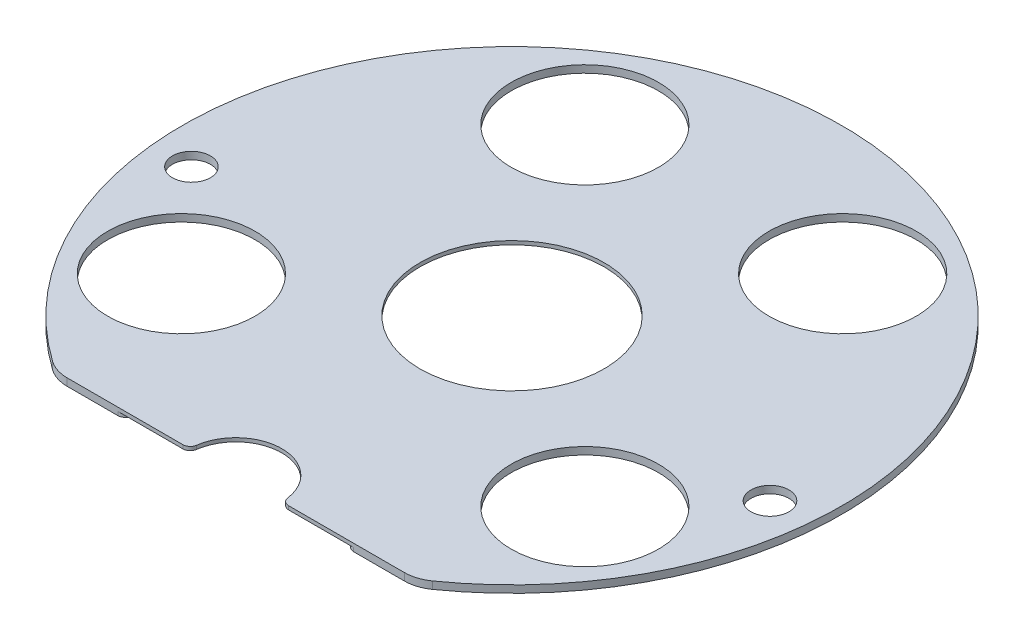
SolidWorks part; units mm, degrees
material "6063-T6"
ref_plane "Front Plane" through (0, 0, 0) normal (0, 0, 1) x (1, 0, 0)
ref_plane "Top Plane" through (0, 0, 0) normal (0, 1, 0) x (1, 0, 0)
ref_plane "Right Plane" through (0, 0, 0) normal (1, 0, 0) x (0, 0, -1)
sketch "Sketch1" plane through (0, 0, 0) normal (0, 1, 0) x (1, 0, 0)
  line L0 (0, 89.5) -> (0, -75) construction
  line L2 (-89.5, 0) -> (89.5, 0) construction
  line L3 (-48.839, -75) -> (48.839, -75)
  arc A0 (48.839, -75) -> (-48.839, -75) centre (0, 0) ccw
  dimension "D1" = 179
  dimension "D2" = 75
extrude "Boss-Extrude1" add sketch "Sketch1" against normal blind 2
sketch "Sketch9" plane through (0, 0, 0) normal (0, 1, 0) x (1, 0, 0)
  line L0 (0, 89.5) -> (0, -75) construction
  line L1 (48.839, -75) -> (-48.839, -75) construction
  line L2 (78.5412, -8.5017) -> (-78.5412, -8.5017) construction
  arc A12 (48.839, -75) -> (-48.839, -75) centre (0, 0) ccw construction
  circle A13 centre (78.5412, -8.5017) radius 5.15
  circle A15 centre (-78.5412, -8.5017) radius 5.15
  point P8 (0, -8.5017)
  dimension "D3" = 10.3
  dimension "D4" = 10.3
  dimension "D2" = 66.4983
  dimension "D1" = 157.0824
extrude "Cut-Extrude3" cut sketch "Sketch9" against normal through all
sketch "Vision Pattern" plane through (0, 0, 0) normal (0, 1, 0) x (1, 0, 0)
  line L0 (64.8074, -55) -> (-64.8074, -55) construction
  line L1 (0, 0) -> (0, -55) construction
  circle A0 centre (0, 0) radius 85 construction
  circle A1 centre (0, 0) radius 25
  circle A2 centre (54.7723, -35) radius 20
  circle A3 centre (-54.7723, -35) radius 20
  circle A4 centre (35, 54.7723) radius 20
  circle A5 centre (-35, 54.7723) radius 20
  circle A6 centre (0, 0) radius 65 construction
  dimension "D1" = 170
  dimension "D3" = 50
  dimension "D4" = 40
  dimension "D2" = 55
  dimension "D5" = 35
  dimension "D8" = 65
  dimension "D6" = 35
  dimension "D7" = 35
extrude "Cut-Extrude4" cut sketch "Vision Pattern" against normal through all
fillet "Fillet1" radius 10 2 edges at (-48.839, -1, 75) (48.839, -1, 75)
ref_plane "Plane2" through (0, 0, -97) normal (0, 0, 1) x (1, 0, 0)
ref_plane "Plane3" through (0, 0, 5) normal (0, 0, 1) x (1, 0, 0)
sketch "Sketch18" plane through (0, 0, 5) normal (0, 0, 1) x (1, 0, 0)
  line L0 (62.8547, -3.6) -> (67.1453, -3.6)
  line L1 (67.1453, -3.6) -> (66.025, -2)
  line L2 (66.025, -2) -> (63.975, -2)
  line L3 (63.975, -2) -> (62.8547, -3.6)
  line L4 (-45.7739, -2) -> (45.7739, -2) construction
  line L6 (-45.7739, -2) -> (45.7739, -2) construction
  point P8 (0, -2)
  point P9 (65, -2)
  dimension "D1" = 55
  dimension "D2" = 55
  dimension "D3" = 1.6
  dimension "D4" = 2.05
  dimension "D5" = 65
extrude "Boss-Extrude4" add sketch "Sketch18" against normal blind 50
mirror "Mirror2" about plane through (0, 0, 0) normal (1, 0, 0) of "Boss-Extrude4"
sketch "Sketch12" plane through (0, -2, 0) normal (0, -1, 0) x (1, 0, 0)
  line L0 (-45.7739, 75) -> (45.7739, 75) construction
  line L1 (-30, 75) -> (30, 75)
  line L2 (-30, 75) -> (-30, -31)
  line L3 (-30, -31) -> (30, -31)
  line L4 (30, 75) -> (30, -31)
  point P6 (0, -31)
  dimension "D1" = 60
  dimension "D2" = 31
extrude "Cut-Extrude5" cut sketch "Sketch12" against normal blind 1
sketch "Sketch16" plane through (0, 0, 0) normal (0, 1, 0) x (1, 0, 0)
  line L0 (-45.7739, -75) -> (45.7739, -75) construction
  circle A0 centre (0, -75) radius 12.5
  dimension "D1" = 25
extrude "Cut-Extrude9" cut sketch "Sketch16" against normal blind 20
sketch "Sketch17" plane through (0, -1, 0) normal (0, -1, 0) x (1, 0, 0)
  line L2 (-30, 75) -> (21.25, 75) construction
  line L3 (30, 75) -> (12.5, 75) construction
  line L4 (-30, 75) -> (-30, -31) construction
  circle A1 centre (-22, -25) radius 0.75
  dimension "D1" = 8
  dimension "D3" = 1.5
  dimension "D4" = 100
extrude "Boss-Extrude3" add sketch "Sketch17" along normal blind 0.425 contours A1
mirror "Mirror1" about plane through (0, 0, 0) normal (1, 0, 0) of "Boss-Extrude3"
chamfer "Chamfer1" distance 1.8 angle 65 6 edges at (63.4148, -2.8, 5) (66.5852, -2.8, 5) (65, -3.6, 5) (-65, -3.6, 5) (-65, -3.6, -45) (65, -3.6, -45)
chamfer "Chamfer2" distance 1 angle 60 8 edges at (-66.5852, -2.8, 2.8555) (-63.4148, -2.8, 2.8555) (63.4148, -2.8, 2.8555) (66.5852, -2.8, 2.8555) (-66.5852, -2.8, -42.8555) (-63.4148, -2.8, -42.8555) (63.4148, -2.8, -42.8555) (66.5852, -2.8, -42.8555)
fillet "Fillet3" radius 0.1 16 edges at (-63.3761, -3.6, 0.1422) (-62.8547, -3.6, -20) (-67.1453, -3.6, -20) (-66.6239, -3.6, 0.1422) (-65, -3.6, 1.1399) (66.6239, -3.6, 0.1422) (67.1453, -3.6, -20) (62.8547, -3.6, -20) (63.3761, -3.6, 0.1422) (65, -3.6, 1.1399) (-65, -3.6, -41.1399) (65, -3.6, -41.1399) (-63.3761, -3.6, -40.1422) (-66.6239, -3.6, -40.1422) (66.6239, -3.6, -40.1422) (63.3761, -3.6, -40.1422)
fillet "Fillet2" radius 0.4 2 edges at (22, -1.425, -25.75) (-22, -1.425, -25.75)
sketch "Sketch19" plane through (0, -3.6, 0) normal (0, -1, 0) x (1, 0, 0)
  line L1 (95.4806, 15.8936) -> (57.8669, 15.8936)
  line L2 (95.4806, 15.8936) -> (95.4806, -73.6368)
  line L3 (95.4806, -73.6368) -> (57.8669, -73.6368)
  line L4 (57.8669, 15.8936) -> (57.8669, -73.6368)
extrude "Test-Print" [suppressed] cut sketch "Sketch19" against normal through all both and the other way through all flip side to cut
fillet "Fillet4" radius 5 2 edges at (-30, -1.5, -31) (30, -1.5, -31)
fillet "Fillet5" radius 2 4 edges at (12.5, -0.5, 75) (-12.5, -0.5, 75) (-30, -1.5, 75) (30, -1.5, 75)
equation "\"D4@Sketch9\"=\"D3@Sketch9\""
equation "\"D1@Vision Pattern\" = 85 * 2"
equation "\"D7@Vision Pattern\"=\"D6@Vision Pattern\""
equation "\"20Gauge\"= .911"
